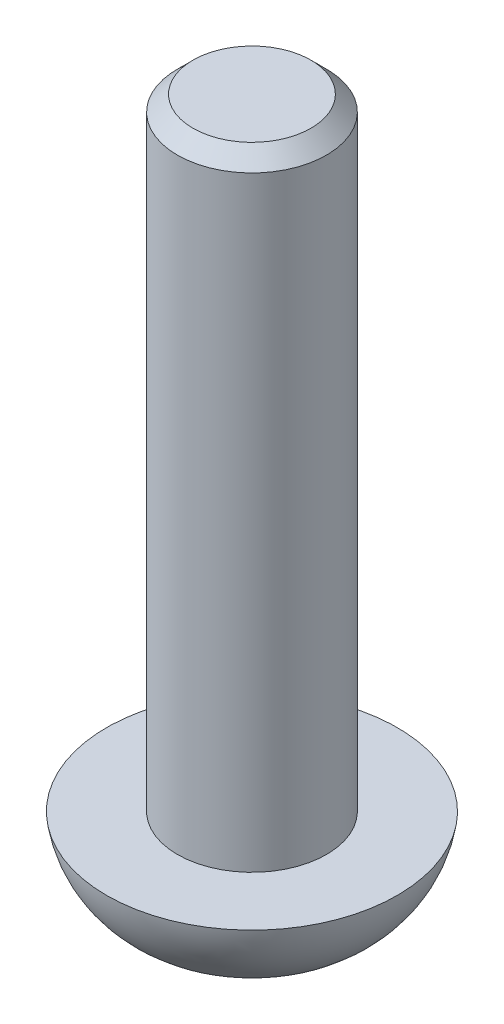
SolidWorks part; units mm, degrees
ref_plane "Front Plane" through (0, 0, 0) normal (0, 0, 1) x (1, 0, 0)
ref_plane "Top Plane" through (0, 0, 0) normal (0, 1, 0) x (1, 0, 0)
ref_plane "Right Plane" through (0, 0, 0) normal (1, 0, 0) x (0, 0, -1)
sketch "Sketch1" plane through (0, 0, 0) normal (0, 1, 0) x (1, 0, 0)
  line L1 (5.404, 0) -> (2.702, 4.68) construction
  line L2 (2.702, 4.68) -> (-2.702, 4.68) construction
  line L3 (-2.702, 4.68) -> (-5.404, 0) construction
  line L4 (-5.404, 0) -> (-2.702, -4.68) construction
  line L5 (-2.702, -4.68) -> (2.702, -4.68) construction
  line L6 (2.702, -4.68) -> (5.404, 0) construction
  circle A0 centre (0, 0) radius 4.68
  dimension "D1" = 9.36
extrude "Boss-Extrude1" add sketch "Sketch1" along normal blind 23
sketch "Sketch2" plane through (0, 23, 0) normal (0, 1, 0) x (1, 0, 0)
  circle A0 centre (0, 0) radius 2.4
  dimension "D1" = 4.8
extrude "Cut-Extrude1" cut sketch "Sketch2" against normal blind 20 flip side to cut
ref_axis "Axis1" through (0, 3, 0) along (0, 1, 0)
chamfer "Chamfer1" distance 0.5 angle 45 1 edges at (0, 23, 2.4)
sketch "Sketch5" plane through (0, 23, 0) normal (0, 1, 0) x (1, 0, 0)
  circle A0 centre (0, 0) radius 2.4
  dimension "D1" = 4.8
curve "Helix/Spiral1" pitch 0.7 height 17 turns 24.2857
ref_plane "Plane1" through (0, 23, 2.4) normal (-0.9989, -0.0464, 0) x (0, 0, 1)
sketch "Sketch8" plane through (0, 0, 0) normal (0, -1, 0) x (1, 0, 0)
  line L1 (1.8706, 0) -> (0.9353, 1.62)
  line L2 (0.9353, 1.62) -> (-0.9353, 1.62)
  line L3 (-0.9353, 1.62) -> (-1.8706, 0)
  line L4 (-1.8706, 0) -> (-0.9353, -1.62)
  line L5 (-0.9353, -1.62) -> (0.9353, -1.62)
  line L6 (0.9353, -1.62) -> (1.8706, 0)
  circle A0 centre (0, 0) radius 1.62 construction
  dimension "D1" = 3.24
extrude "Cut-Extrude2" cut sketch "Sketch8" against normal blind 2.5
fillet "Fillet1" radius 3.5 1 edges at (0, 0, 4.68)
